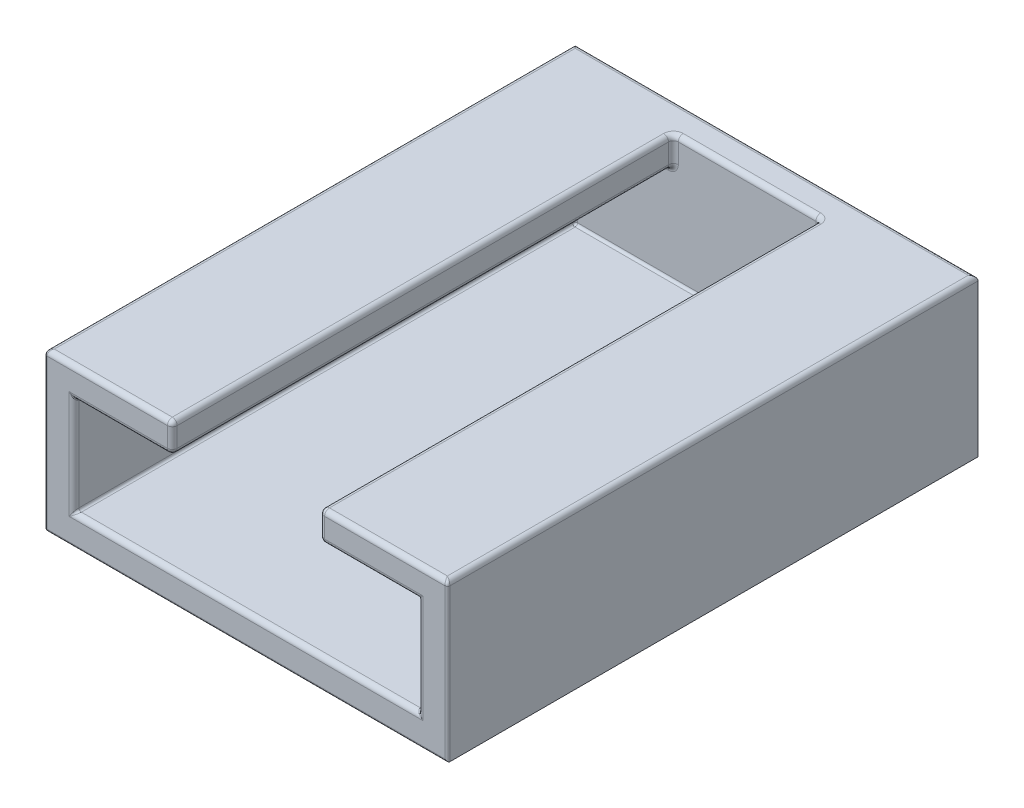
SolidWorks part; units mm, degrees
material "ABS"
ref_plane "Plan de face" through (0, 0, 0) normal (0, 0, 1) x (1, 0, 0)
ref_plane "Plan de dessus" through (0, 0, 0) normal (0, 1, 0) x (1, 0, 0)
ref_plane "Plan de droite" through (0, 0, 0) normal (1, 0, 0) x (0, 0, -1)
sketch "Esquisse1" plane through (0, 0, 0) normal (0, 0, 1) x (1, 0, 0)
  line L0 (0, 0) -> (41, 0)
  line L1 (41, 0) -> (41, 16)
  line L2 (41, 16) -> (28, 16)
  line L3 (28, 16) -> (28, 13)
  line L4 (28, 13) -> (38, 13)
  line L5 (38, 13) -> (38, 3)
  line L6 (38, 3) -> (3, 3)
  line L7 (3, 3) -> (3, 13)
  line L8 (3, 13) -> (13, 13)
  line L9 (13, 13) -> (13, 16)
  line L10 (13, 16) -> (0, 16)
  line L11 (0, 16) -> (0, 0)
  dimension "D1" = 41
  dimension "D2" = 10
  dimension "D3" = 10
  dimension "D4" = 35
  dimension "D5" = 3
  dimension "D6" = 10
  dimension "D7" = 3
  dimension "D8" = 3
  dimension "D9" = 3
  dimension "D10" = 10
extrude "Boss.-Extru.1" add sketch "Esquisse1" along normal blind 51
sketch "Esquisse4" plane through (0, 0, 0) normal (0, 0, -1) x (-1, 0, 0)
  line L1 (-41, 0) -> (0, 0)
  line L2 (-41, 0) -> (-41, 16)
  line L3 (-41, 16) -> (0, 16)
  line L4 (0, 0) -> (0, 16)
extrude "Boss.-Extru.3" add sketch "Esquisse4" along normal blind 3
fillet "Congé1" radius 0.5 21 edges at (33, 13, 0) (8, 13, 0) (6.5, 16, 51) (28, 14.5, 0) (13, 14.5, 0) (28, 13, 25.5) (0, 16, 24) (20.5, 16, -3) (20.5, 16, 0) (28, 16, 25.5) (13, 13, 25.5) (13, 16, 25.5) (28, 14.5, 51) (13, 14.5, 51) (8, 13, 51) (3, 8, 51) (20.5, 3, 51) (41, 16, 24) (38, 8, 51) (33, 13, 51) (34.5, 16, 51)
sketch "Esquisse5" plane through (0, 0, -3) normal (0, 0, -1) x (-1, 0, 0)
  line L0 (-20.5, 0) -> (-20.5, 15.5) construction
  line L1 (-41, 0) -> (0, 0) construction
  line L2 (0, 15.5) -> (-41, 15.5) construction
fillet "Congé2" radius 0.25 18 edges at (2.8536, 13.1464, 50.8536) (38.1464, 13.1464, 50.8536) (38.1464, 2.8536, 50.8536) (2.8536, 2.8536, 50.8536) (0.1464, 15.8536, 50.8536) (40.8536, 15.8536, 50.8536) (3, 13, 25.5) (3, 12.8536, 0.1464) (3, 7.75, 0) (38, 7.75, 0) (38, 12.8536, 0.1464) (38, 13, 25.5) (20.5, 3, 0) (38, 3, 25.25) (3, 3, 25.25) (20.5, 0, 51) (0, 7.75, 51) (41, 7.75, 51)
fillet "Congé3" radius 0.25 2 edges at (0.0732, 0.0732, 50.9268) (0, 0, 23.875)
